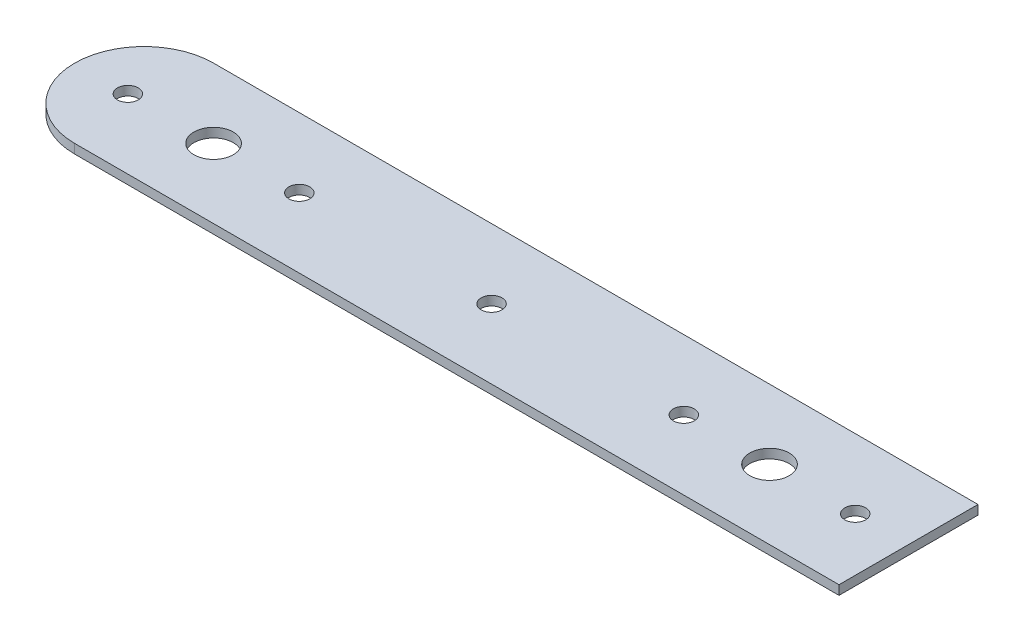
SolidWorks part; units mm, degrees
ref_plane "前视" through (0, 0, 0) normal (0, 0, 1) x (1, 0, 0)
ref_plane "上视" through (0, 0, 0) normal (0, 1, 0) x (1, 0, 0)
ref_plane "右视" through (0, 0, 0) normal (1, 0, 0) x (0, 0, -1)
sketch "草图1" plane through (0, 0, 0) normal (0, 1, 0) x (1, 0, 0)
  line L1 (-90, 15) -> (90, 15)
  line L2 (-90, 15) -> (-90, -15)
  line L3 (-90, -15) -> (90, -15)
  line L4 (90, 15) -> (90, -15)
  line L5 (-90, 15) -> (90, -15) construction
  line L6 (-90, -15) -> (90, 15) construction
  point P0 (0, 0)
  dimension "D1" = 180
  dimension "D2" = 30
extrude "凸台-拉伸1" add sketch "草图1" along normal blind 2 contours L2 | L2 | L3 L1 | L4 | L4 region at (0, 0, 0)
sketch "草图2" plane through (0, 2, 0) normal (0, 1, 0) x (1, 0, 0)
  circle A0 centre (-60, 0) radius 4.25
  circle A1 centre (60, 0) radius 4.25
  circle A2 centre (0, 0) radius 2.25
  dimension "D1" = 8.5
  dimension "D2" = 8.5
  dimension "D5" = 4.5
  dimension "D3" = 120
  dimension "D4" = 60
extrude "切除-拉伸1" cut sketch "草图2" against normal up to next
fillet "圆角1" 2 edges at (-90, 1, 15) (-90, 1, -15) type full round first side face at (0, 1, 15) second side face at (0, 1, -15) middle face at (-90, 1, 0)
sketch "草图3" plane through (0, 2, 0) normal (0, 1, 0) x (1, 0, 0)
  circle A0 centre (-78.5, 0) radius 2.25
  circle A1 centre (-41.5, 0) radius 2.25
  circle A2 centre (41.5, 0) radius 2.25
  circle A3 centre (78.5, 0) radius 2.25
  circle A4 centre (-60, 0) radius 4.25 construction
  circle A5 centre (60, 0) radius 4.25 construction
  dimension "D2" = 18.5
  dimension "D3" = 4.5
  dimension "D4" = 4.5
  dimension "D6" = 18.5
  dimension "D7" = 4.5
  dimension "D8" = 4.5
  dimension "D1" = 37
  dimension "D5" = 37
extrude "切除-拉伸2" cut sketch "草图3" against normal up to next
